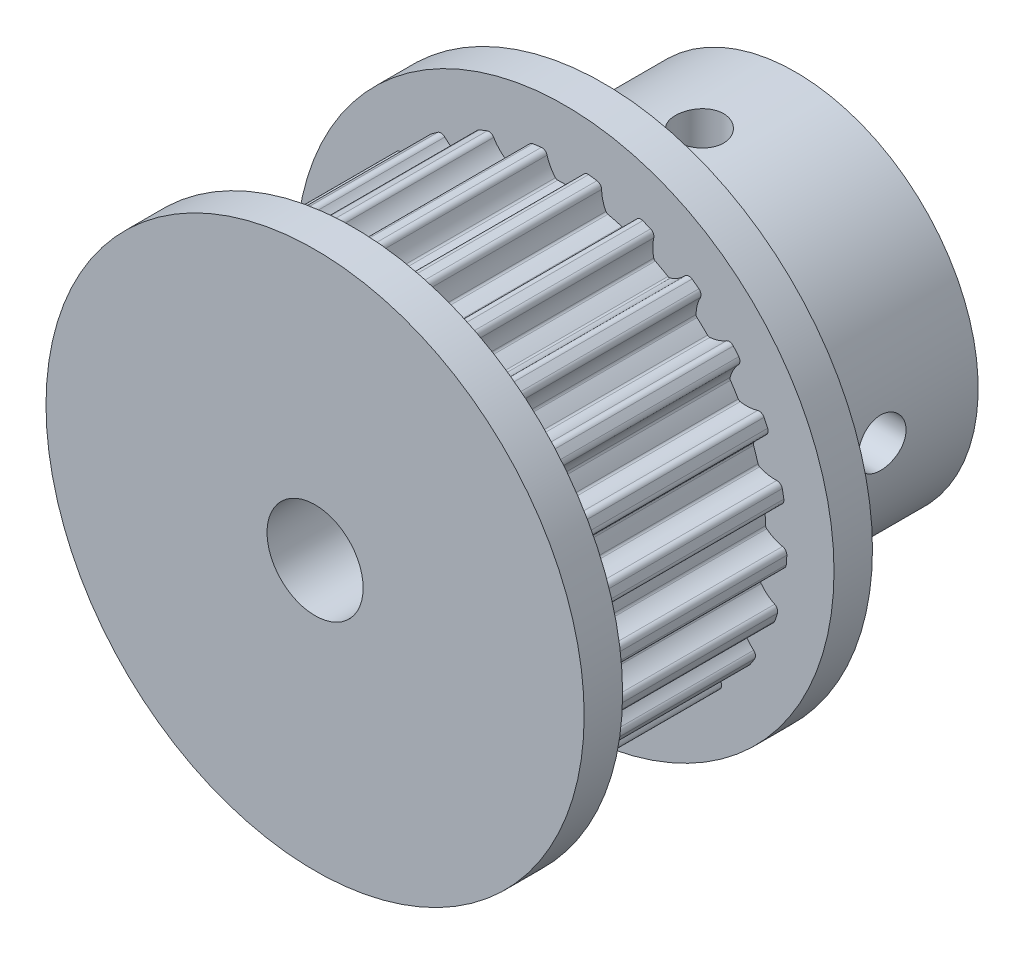
SolidWorks part; units mm, degrees
material "6061-T6 (SS)"
ref_plane "前基準面" through (0, 0, 0) normal (0, 0, 1) x (1, 0, 0)
ref_plane "上基準面" through (0, 0, 0) normal (0, 1, 0) x (1, 0, 0)
ref_plane "右基準面" through (0, 0, 0) normal (1, 0, 0) x (0, 0, -1)
sketch "草圖1" plane through (0, 0, 0) normal (0, 0, 1) x (1, 0, 0)
  circle A0 centre (0, 0) radius 11.555
  dimension "D1" = 23.11
extrude "填料-伸長1" add sketch "草圖1" along normal mid plane 11
sketch "草圖2" plane through (0, 0, 5.5) normal (0, 0, 1) x (1, 0, 0)
  line L0 (0, 0) -> (0, 11.809) construction
  line L1 (-0.975, 11.809) -> (0.975, 11.809) construction
  arc A0 (-0.3761, 10.4382) -> (0.3761, 10.4382) centre (0, 0) cw
  circle A1 centre (0, 0) radius 11.555 construction
  arc A2 (-1.2291, 11.4894) -> (-0.9293, 11.2853) centre (-1.1993, 11.211) cw
  arc A3 (-0.9293, 11.2853) -> (-0.493, 10.4878) centre (0.975, 11.809) ccw
  arc A4 (-0.493, 10.4878) -> (-0.3761, 10.4382) centre (-0.3815, 10.5881) ccw
  arc A5 (0.493, 10.4878) -> (0.3761, 10.4382) centre (0.3815, 10.5881) cw
  arc A6 (0.9293, 11.2853) -> (0.493, 10.4878) centre (-0.975, 11.809) cw
  arc A7 (1.2291, 11.4894) -> (0.9293, 11.2853) centre (1.1993, 11.211) ccw
  point P6 (0, 10.445)
  point P18 (0, 11.555)
  dimension "D1" = 1.11
  dimension "D2" = 0.15
  dimension "D3" = 1.975
  dimension "D4" = 0.28
  dimension "D5" = 1.95
  dimension "D6" = 0.254
extrude "除料-伸長1" cut sketch "草圖2" against normal through all and the other way through all flip side to cut
pattern_circular "環狀複製排列1" count 25 over 360 about axis through (0, 0, 5.5) along (0, 0, 1) of "除料-伸長1"
sketch "草圖3" plane through (0, 0, 5.5) normal (0, 0, 1) x (1, 0, 0)
  circle A0 centre (0, 0) radius 14
  dimension "D1" = 28
extrude "填料-伸長2" add sketch "草圖3" along normal blind 2
mirror "鏡射1" about plane through (0, 0, 0) normal (0, 0, 1) of "填料-伸長2"
sketch "草圖5" plane through (0, 0, -7.5) normal (0, 0, -1) x (-1, 0, 0)
  circle A0 centre (0, 0) radius 9.5
  dimension "D1" = 19
extrude "填料-伸長3" add sketch "草圖5" along normal blind 10
sketch "草圖4" plane through (0, 0, 7.5) normal (0, 0, 1) x (1, 0, 0)
  circle A0 centre (0, 0) radius 2.5
  dimension "D1" = 5
extrude "除料-伸長2" cut sketch "草圖4" against normal through all
hole_wizard "M3x0.5 螺紋孔1" positions "草圖6" profile "草圖7" tap size "M3x0.5" standard "Ansi Metric" end condition through all
sketch "草圖6" plane through (0, 0, 0) normal (0, 1, 0) x (1, 0, 0)
  point P0 (0, 12.5)
sketch "草圖7" plane through (0, 0, -12.5) normal (1, 0, 0) x (0, 0, -1)
  line L0 (0, 0) -> (0, 14)
  line L1 (0, 14) -> (1.25, 14)
  line L2 (1.25, 14) -> (1.25, 0)
  line L5 (1.25, 0) -> (0, 0)
  line L11 (0, -6.35) -> (0, 107.95) construction
  dimension "貫穿螺孔鑽直徑" = 2.5
  dimension "貫穿螺孔鑽深度" = 14
pattern_circular "環狀複製排列2" count 2 every 90 about axis through (0, 0, -17.5) along (0, 0, -1) of "M3x0.5 螺紋孔1"
